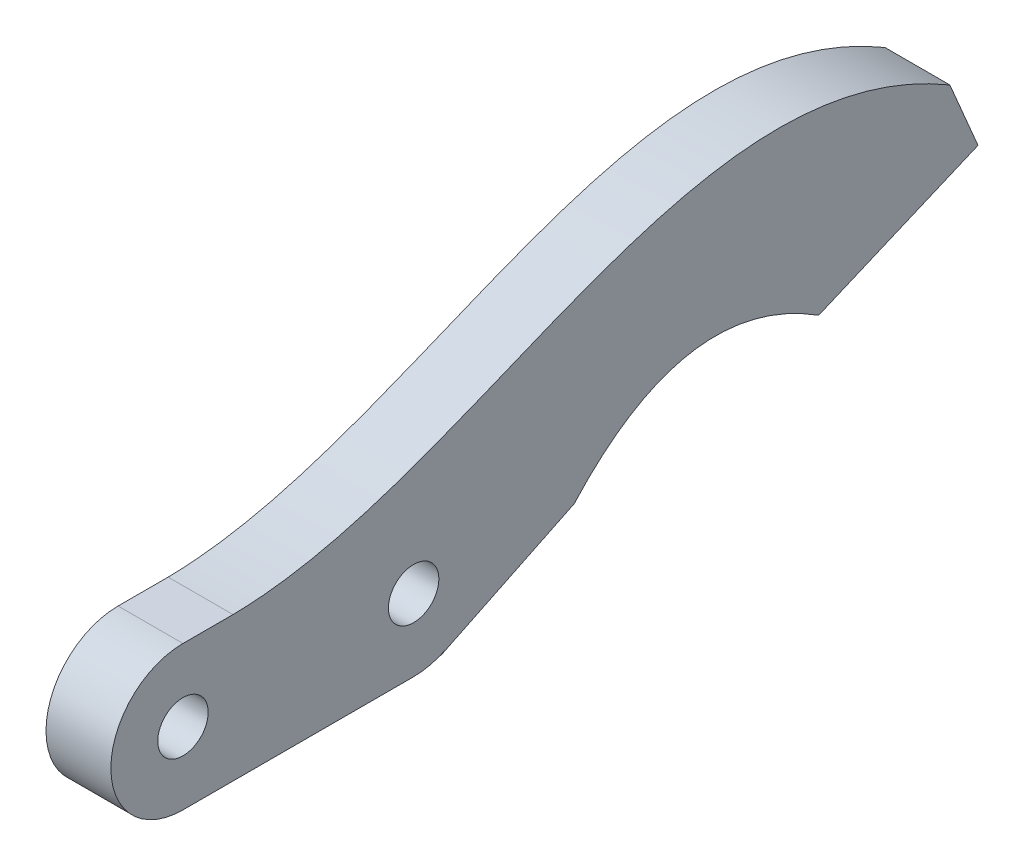
SolidWorks part; units mm, degrees
ref_plane "Front Plane" through (0, 0, 0) normal (0, 0, 1) x (1, 0, 0)
ref_plane "Top Plane" through (0, 0, 0) normal (0, 1, 0) x (1, 0, 0)
ref_plane "Right Plane" through (0, 0, 0) normal (1, 0, 0) x (0, 0, -1)
sketch "Sketch1" plane through (0, 0, 0) normal (1, 0, 0) x (0, 0, -1)
  line L1 (0, 0) -> (27, 0)
  line L2 (0, 0) -> (0, 10)
  line L3 (0, 10) -> (21, 10)
  circle A0 centre (5, 5) radius 1.75
  circle A1 centre (5, 5) radius 5
  circle A2 centre (21, 5) radius 5
  circle A3 centre (21, 5) radius 1.75
  dimension "D7" = 3.5
  dimension "D11" = 10
  dimension "D2" = 3.5
  dimension "D1" = 10
  dimension "D8" = 5
  dimension "D9" = 5
  dimension "D10" = 16
extrude "Boss-Extrude1" add sketch "Sketch1" along normal blind 4.5 contours A1 A0 | A2 L3 A1 L1 | A2 A3 | L2 A1 | L1 A1 region at (0, 5, -13) region at (0, 1.5645, -1.5645) region at (0, 5, -16.1414)
sketch "Sketch2" plane through (4.5, 0, 5.9488) normal (1, 0, 0) x (0, 0, -1)
  line L14 (5.0017, 10.1224) -> (26.9995, 9.8127)
  line L20 (28.8247, 0.3277) -> (38.0854, 4.8241)
  line L21 (55.0455, 7.6656) -> (66.0942, 12.3481)
  line L22 (66.0942, 12.3481) -> (64.1432, 16.9517)
  arc A4 (26.5704, -0.1739) -> (26.9995, 9.8127) centre (26.6408, 4.8256) ccw
  spline S0 degree 2 poles (38.0854, 4.8241) (45.8792, 13.4817) (55.0455, 7.6656) knots 0 0 0 1 1 1
  spline S1 degree 3 poles (64.1432, 16.9517) (46.3659, 27.4751) (31.1773, 9.7539) (13.695, 10) knots 0 0 0 0 1 1 1 1
  point P2 (27, 5)
  line M1 (26.9488, 10) -> (10.9488, 10)
  arc M4 (26.9488, 0) -> (26.9488, 10) centre (26.9488, 5) ccw
  dimension "D3" = 5
  dimension "D4" = 12
extrude "Boss-Extrude2" add sketch "Sketch2" against normal blind 4.5 contours M1 M4 region at (4.5, 12.8182, -39.5491)
